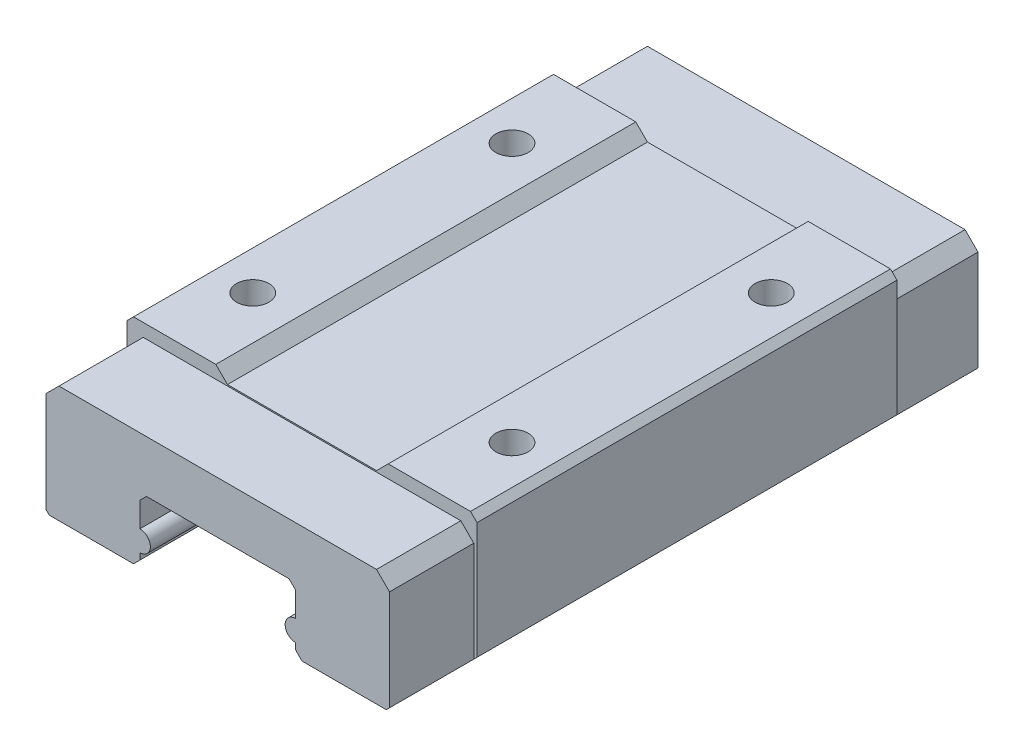
SolidWorks part; units mm, degrees
material "1023 Carbon Steel Sheet (SS)"
ref_plane "Front Plane" through (0, 0, 0) normal (0, 0, 1) x (1, 0, 0)
ref_plane "Top Plane" through (0, 0, 0) normal (0, 1, 0) x (1, 0, 0)
ref_plane "Right Plane" through (0, 0, 0) normal (1, 0, 0) x (0, 0, -1)
sketch "Master Sketch" plane through (0, 0, 0) normal (0, 1, 0) x (1, 0, 0)
  line L0 (-10, -10) -> (10, 10) construction
  line L1 (-13.25, -22.7) -> (13.25, -22.7)
  line L2 (-13.25, -22.7) -> (-13.25, 22.7)
  line L3 (-13.25, 22.7) -> (13.25, 22.7)
  line L4 (13.25, -22.7) -> (13.25, 22.7)
  line L5 (-13.25, -22.7) -> (13.25, 22.7) construction
  line L6 (-13.25, 22.7) -> (13.25, -22.7) construction
  line L7 (-13.5, -16.2) -> (13.5, -16.2)
  line L8 (-13.5, -16.2) -> (-13.5, 16.2)
  line L9 (-13.5, 16.2) -> (13.5, 16.2)
  line L10 (13.5, -16.2) -> (13.5, 16.2)
  line L11 (-13.5, -16.2) -> (13.5, 16.2) construction
  line L12 (-13.5, 16.2) -> (13.5, -16.2) construction
  point P0 (0, 0)
  point P5 (0, 0)
  point P11 (10, 10)
  point P12 (-10, 10)
  point P13 (10, -10)
  point P14 (-10, -10)
  dimension "D1" = 26.5
  dimension "D2" = 45.4
  dimension "D3" = 32.4
  dimension "D4" = 20
  dimension "D5" = 20
  dimension "D6" = 27
ref_plane "BlockMaxHeightPlane" through (0, 10, 0) normal (0, 1, 0) x (1, 0, 0)
sketch "MainBlockSketch" plane through (0, 0, 0) normal (0, 1, 0) x (1, 0, 0)
  line L0 (-13.25, -22.7) -> (13.25, -22.7) construction
  line L1 (13.25, -22.7) -> (13.25, 22.7) construction
  line L2 (-13.25, 22.7) -> (13.25, 22.7) construction
  line L3 (-13.25, -22.7) -> (-13.25, 22.7) construction
  line L4 (-13.25, -22.7) -> (13.25, -22.7)
  line L5 (13.25, -22.7) -> (13.25, 22.7)
  line L6 (-13.25, 22.7) -> (13.25, 22.7)
  line L7 (-13.25, -22.7) -> (-13.25, 22.7)
extrude "MainBlock" add sketch "MainBlockSketch" along normal blind 9
sketch "FacedSurfaceSketch" plane through (0, 0, 0) normal (0, 1, 0) x (1, 0, 0)
  line L0 (-13.5, -16.2) -> (13.5, -16.2) construction
  line L3 (-13.5, 16.2) -> (13.5, 16.2) construction
  line L4 (-13.5, -16.2) -> (13.5, -16.2)
  line L7 (-13.5, 16.2) -> (13.5, 16.2)
  line L8 (-13.5, 16.2) -> (-13.5, -16.2)
  line L9 (13.5, 16.2) -> (13.5, -16.2)
extrude "FacedSurface" add sketch "FacedSurfaceSketch" along normal up to surface (10 mm away) up to plane "BlockMaxHeightPlane"
hole_wizard "M3x0.5 Tapped Hole1" positions "Sketch4" profile "Sketch5" tap size "M3x0.5" standard "ANSI Metric"
sketch "Sketch4" plane through (0, 10, 0) normal (0, 1, 0) x (1, 0, 0)
  point P0 (-10, 10)
  point P3 (10, 10)
  point P6 (10, -10)
  point P9 (-10, -10)
sketch "Sketch5" plane through (-10, 10, -10) normal (1, 0, 0) x (0, 0, 1)
  line L0 (0, 0) -> (0, 9.2511)
  line L1 (0, 9.2511) -> (1.25, 8.5)
  line L2 (1.25, 8.5) -> (1.25, 0)
  line L5 (1.25, 0) -> (0, 0)
  line L10 (0, 9.2511) -> (-1.25, 8.5) construction
  line L11 (0, -6.35) -> (0, 107.95) construction
  dimension "Tap Drill Dia." = 2.5
  dimension "Tap Drill Depth" = 8.5
  dimension "Drill Angle" = 118
cosmetic thread "Hole Thread1" parameters "D1"=7, "D2"=3
cosmetic thread "Hole Thread2" parameters "D1"=7, "D2"=3
cosmetic thread "Hole Thread3" parameters "D1"=7, "D2"=3
cosmetic thread "Hole Thread4" parameters "D1"=7, "D2"=3
sketch "RailSlotSketch" plane through (0, 0, 0) normal (0, 0, 1) x (1, 0, 0)
  line L0 (-6, 2.59) -> (-6, 5)
  line L1 (-6, 0) -> (6, 0)
  line L2 (-6, 0) -> (-6, 0.99)
  line L3 (-6, 5) -> (6, 5)
  line L4 (6, 0) -> (6, 0.99)
  line L5 (-6, 0) -> (6, 5) construction
  line L6 (-6, 5) -> (6, 0) construction
  line L7 (6, 2.59) -> (6, 5)
  arc A0 (-6, 2.59) -> (-6, 0.99) centre (-6, 1.79) cw
  arc A1 (6, 2.59) -> (6, 0.99) centre (6, 1.79) ccw
  point P0 (0, 2.5)
  dimension "D3" = 0.8
  dimension "D1" = 5
  dimension "D2" = 12
  dimension "D4" = 3.21
extrude "Rail Slot" cut sketch "RailSlotSketch" against normal through all both and the other way through all
sketch "Internal Dip Sketch" plane through (0, 10, 0) normal (0, 1, 0) x (1, 0, 0)
  line L1 (6.75, -16.2) -> (-6.75, -16.2)
  line L2 (6.75, -16.2) -> (6.75, 16.2)
  line L3 (6.75, 16.2) -> (-6.75, 16.2)
  line L4 (-6.75, -16.2) -> (-6.75, 16.2)
  line L5 (6.75, -16.2) -> (-6.75, 16.2) construction
  line L6 (6.75, 16.2) -> (-6.75, -16.2) construction
  line L7 (-13.5, 16.2) -> (13.5, 16.2) construction
  line L8 (-13.25, 10) -> (-6.75, 10) construction
  line L9 (-13.25, -22.7) -> (-13.25, 22.7) construction
  point P10 (-10, 10)
extrude "Internal Dip" cut sketch "Internal Dip Sketch" against normal blind 0.9
chamfer "Internal Chamfer" distance 0.5 angle 45 2 edges at (6, 5, 0) (-6, 5, 0)
chamfer "Cosmetic Chamfers" distance 1 angle 45 6 edges at (-6.75, 9.1, 0) (6.75, 9.1, 0) (13.25, 9, 19.45) (-13.25, 9, 19.45) (-13.25, 9, -19.45) (13.25, 9, -19.45)
chamfer "Smaller Cosmetic Chamfers" distance 0.5 angle 45 6 edges at (13.5, 10, 0) (-13.5, 10, 0) (-13.5, 0, 0) (13.5, 0, 0) (6, 0, 0) (-6, 0, 0)
